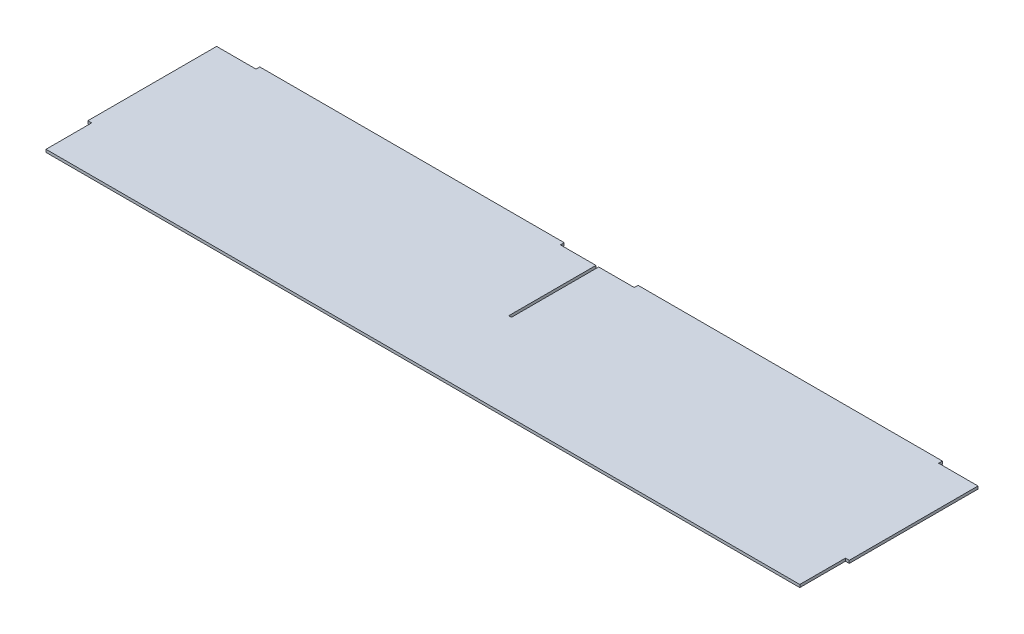
SolidWorks part; units mm, degrees
material "6061-T6 (SS)"
ref_plane "X-Y Datum" through (0, 0, 0) normal (0, 0, 1) x (1, 0, 0)
ref_plane "X-Z Datum" through (0, 0, 0) normal (0, 1, 0) x (1, 0, 0)
ref_plane "Y-Z Datum" through (0, 0, 0) normal (1, 0, 0) x (0, 0, -1)
sketch "Sketch1" plane through (0, 0, 0) normal (0, 1, 0) x (1, 0, 0)
  line L1 (-317.6778, 72.771) -> (317.6778, 72.771)
  line L2 (-317.6778, 72.771) -> (-317.6778, -72.771)
  line L3 (-317.6778, -72.771) -> (317.6778, -72.771)
  line L4 (317.6778, 72.771) -> (317.6778, -72.771)
  line L5 (-317.6778, 72.771) -> (317.6778, -72.771) construction
  line L6 (-317.6778, -72.771) -> (317.6778, 72.771) construction
  point P0 (0, 0)
  dimension "D1" = 635.3556
  dimension "D2" = 145.542
extrude "Boss-Extrude1" add sketch "Sketch1" along normal mid plane 2.286
sketch "Sketch2" plane through (0, 0, -72.771) normal (0, 0, -1) x (-1, 0, 0)
  line L0 (-317.6778, 1.143) -> (317.6778, 1.143) construction
  line L20 (-317.6778, -1.143) -> (317.6778, -1.143) construction
  line L21 (-284.8229, -1.143) -> (-30.8229, -1.143)
  line L22 (30.8229, -1.143) -> (284.8229, -1.143)
  line L40 (30.8229, -1.143) -> (30.8229, 1.143)
  line L41 (30.8229, 1.143) -> (284.8229, 1.143)
  line L42 (284.8229, 1.143) -> (284.8229, -1.143)
  line L56 (-284.8229, -1.143) -> (-284.8229, 1.143)
  line L57 (-284.8229, 1.143) -> (-30.8229, 1.143)
  line L58 (-30.8229, 1.143) -> (-30.8229, -1.143)
extrude "Boss-Extrude2" add sketch "Sketch2" along normal blind 3.175
sketch "Sketch3" plane through (0, -1.143, 0) normal (0, -1, 0) x (1, 0, 0)
  line L0 (-314.3758, 72.898) -> (-314.3758, 34.544)
  line L1 (-317.6778, 72.771) -> (-314.5028, 72.771)
  line L2 (-317.6778, 72.771) -> (-317.6778, 34.671)
  line L3 (-317.6778, 34.671) -> (-314.5028, 34.671)
  line L4 (-314.5028, 72.771) -> (-314.5028, 34.671)
  line L5 (-317.8048, 34.544) -> (-314.3758, 34.544)
  line L6 (-317.8048, 72.898) -> (-317.8048, 34.544)
  line L7 (-317.8048, 72.898) -> (-314.3758, 72.898)
  line M6 (317.6778, 72.771) -> (-317.6778, 72.771)
  line M7 (-317.6778, 72.771) -> (-317.6778, -72.771)
  dimension "D1" = 38.1
  dimension "D2" = 3.175
  dimension "D3" = 0.127
extrude "Cut-Extrude1" cut sketch "Sketch3" against normal through all contours L4 L3 M6 M7 region at (-316.0903, -1.143, 53.721)
mirror "Mirror1" about plane through (0, 0, 0) normal (1, 0, 0) of "Cut-Extrude1"
sketch "Sketch4" plane through (0, -1.143, 0) normal (0, -1, 0) x (1, 0, 0)
  line L0 (30.8229, -72.771) -> (-30.8229, -72.771) construction
  line L1 (-1.143, -72.771) -> (1.143, -72.771)
  line L2 (-1.143, -72.771) -> (-1.143, 0)
  line L3 (-1.143, 0) -> (1.143, 0)
  line L4 (1.143, -72.771) -> (1.143, 0)
  line L5 (-1.143, -75.946) -> (-1.143, -72.771) construction
  line L6 (-1.3081, -72.9361) -> (-1.3081, 0.1651)
  line L7 (-1.3081, 0.1651) -> (1.3081, 0.1651)
  line L8 (1.3081, -72.9361) -> (1.3081, 0.1651)
  line L9 (-1.3081, -72.9361) -> (1.3081, -72.9361)
  line M15 (-30.8229, -72.771) -> (30.8229, -72.771)
  dimension "D1" = 2.286
  dimension "D2" = 72.771
  dimension "D3" = 0.1651
extrude "Cut-Extrude2" cut sketch "Sketch4" against normal through all contours L4 L3 L2 M15 region at (0, -1.143, -36.3855)
